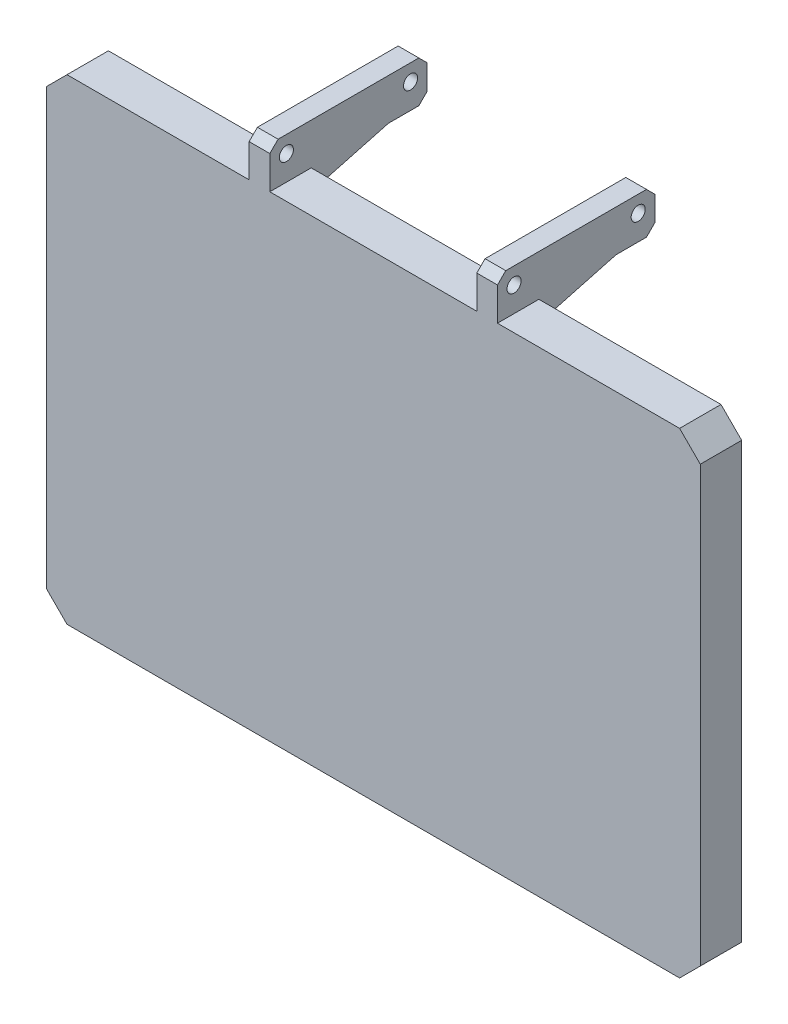
SolidWorks part; units mm, degrees
ref_plane "Front Plane" through (0, 0, 0) normal (0, 0, 1) x (1, 0, 0)
ref_plane "Top Plane" through (0, 0, 0) normal (0, 1, 0) x (1, 0, 0)
ref_plane "Right Plane" through (0, 0, 0) normal (1, 0, 0) x (0, 0, -1)
sketch "Sketch1" plane through (0, 0, 0) normal (0, 0, 1) x (1, 0, 0)
  line L1 (-79, -57.5) -> (79, -57.5)
  line L2 (-79, -57.5) -> (-79, 57.5)
  line L3 (-79, 57.5) -> (79, 57.5)
  line L4 (79, -57.5) -> (79, 57.5)
  line L5 (-79, -57.5) -> (79, 57.5) construction
  line L6 (-79, 57.5) -> (79, -57.5) construction
  point P0 (0, 0)
  dimension "D1" = 115
  dimension "D2" = 158
extrude "Boss-Extrude1" add sketch "Sketch1" along normal blind 10
sketch "Sketch2" plane through (0, 0, 0) normal (0, 0, -1) x (-1, 0, 0)
  line L1 (-74, -52.5) -> (74, -52.5)
  line L2 (-74, -52.5) -> (-74, 52.5)
  line L3 (-74, 52.5) -> (74, 52.5)
  line L4 (74, -52.5) -> (74, 52.5)
  line L5 (-74, -52.5) -> (74, 52.5) construction
  line L6 (-74, 52.5) -> (74, -52.5) construction
  point P0 (0, 0)
  dimension "D1" = 148
  dimension "D2" = 105
extrude "Cut-Extrude1" cut sketch "Sketch2" against normal blind 2
sketch "Sketch3" plane through (0, 0, 0) normal (0, 0, -1) x (-1, 0, 0)
  line L0 (-74, 42.5) -> (-64, 52.5)
  line L3 (-74, 52.5) -> (-74, -52.5) construction
  line L4 (74, 52.5) -> (-74, 52.5) construction
  line L5 (-64, 52.5) -> (-74, 52.5)
  line L7 (-74, 52.5) -> (-74, 42.5)
  line L8 (0, 0) -> (0, 52.5) construction
  line L9 (0, 0) -> (-74, 0) construction
  line L11 (-74, 52.5) -> (-74, -52.5) construction
  line L12 (74, 52.5) -> (74, 42.5)
  line L13 (64, 52.5) -> (74, 52.5)
  line L14 (74, 42.5) -> (64, 52.5)
  line L16 (-74, -52.5) -> (-74, -42.5)
  line L17 (-64, -52.5) -> (-74, -52.5)
  line L18 (-74, -42.5) -> (-64, -52.5)
  line L19 (74, -42.5) -> (64, -52.5)
  line L20 (64, -52.5) -> (74, -52.5)
  line L21 (74, -52.5) -> (74, -42.5)
  dimension "D1" = 10
extrude "Boss-Extrude2" add sketch "Sketch3" against normal blind 1.5
sketch "Sketch4" plane through (0, 0, 10) normal (0, 0, 1) x (1, 0, 0)
  line L0 (0, 0) -> (0, 57.5) construction
  line L1 (79, 57.5) -> (-79, 57.5) construction
  line L2 (30, 57.5) -> (30, 67.5)
  line L3 (-25, 57.5) -> (-30, 57.5)
  line L4 (-25, 57.5) -> (-25, 67.5)
  line L5 (-25, 67.5) -> (-30, 67.5)
  line L6 (-30, 57.5) -> (-30, 67.5)
  line L7 (25, 67.5) -> (30, 67.5)
  line L8 (25, 57.5) -> (25, 67.5)
  line L9 (25, 57.5) -> (30, 57.5)
  dimension "D1" = 5
  dimension "D2" = 10
  dimension "D3" = 50
extrude "Boss-Extrude3" add sketch "Sketch4" against normal blind 38
hole_wizard "M3 Clearance Hole1" positions "Sketch7" profile "Sketch8" hole size "M3" standard "ISO" end condition through all
sketch "Sketch7" plane through (30, 0, 0) normal (1, 0, 0) x (0, 0, -1)
  line L0 (-10, 57.5) -> (-10, 67.5) construction
  line L1 (28, 67.5) -> (-10, 67.5) construction
  point P0 (24, 63.5)
  point P2 (-6, 63.5)
  dimension "D1" = 30
  dimension "D2" = 4
  dimension "D3" = 4
sketch "Sketch8" plane through (30, 63.5, -24) normal (0, 1, 0) x (0, 0, -1)
  line L0 (0, 0) -> (0, 109)
  line L1 (0, 109) -> (1.7, 109)
  line L2 (1.7, 109) -> (1.7, 0)
  line L5 (1.7, 0) -> (0, 0)
  line L11 (0, -6.35) -> (0, 107.95) construction
  dimension "Thru Hole Dia." = 3.4
  dimension "Thru Hole Depth" = 109
chamfer "Chamfer3" distance 2 angle 45 4 edges at (-27.5, 67.5, -28) (27.5, 67.5, -28) (27.5, 67.5, 10) (-27.5, 67.5, 10)
chamfer "Chamfer4" distance 5 angle 75 2 edges at (27.5, 57.5, 0) (-27.5, 57.5, 0) first distance on face at (0, 0, 0)
chamfer "Chamfer5" distance 5 angle 45 4 edges at (79, 57.5, 5) (-79, 57.5, 5) (-79, -57.5, 5) (79, -57.5, 5)
chamfer "Chamfer6" distance 2 angle 45 2 edges at (-27.5, 57.5, -28) (27.5, 57.5, -28)
